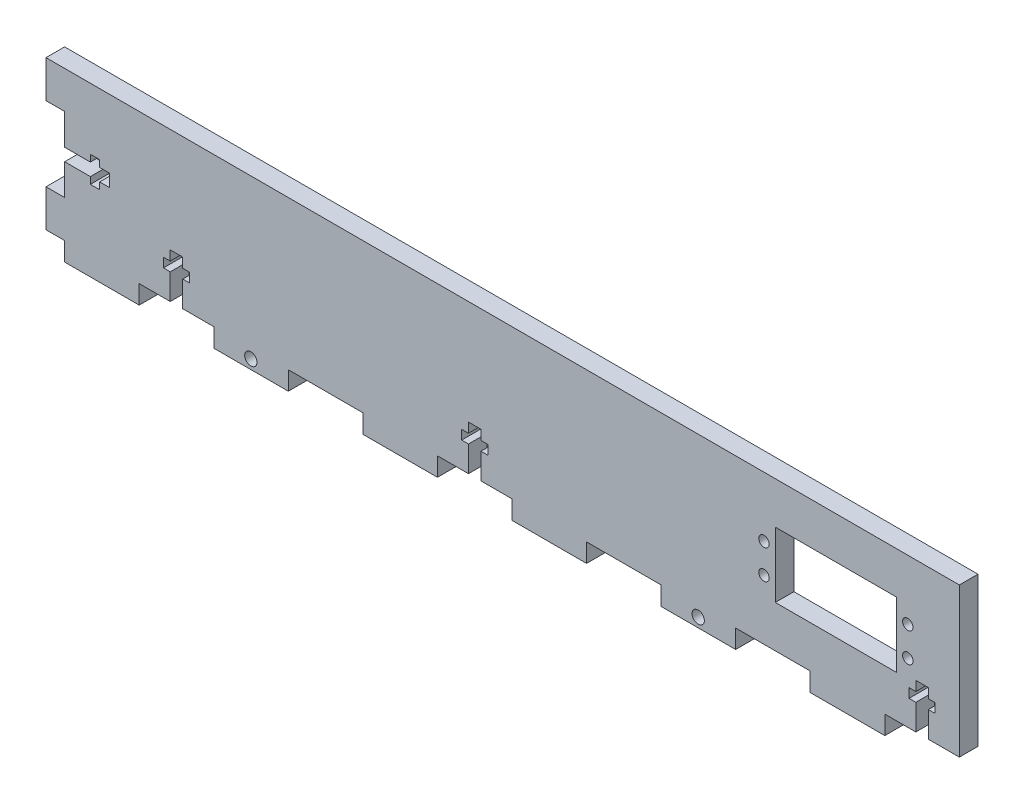
SolidWorks part; units mm, degrees
ref_plane "Front Plane" through (0, 0, 0) normal (0, 0, 1) x (1, 0, 0)
ref_plane "Top Plane" through (0, 0, 0) normal (0, 1, 0) x (1, 0, 0)
ref_plane "Right Plane" through (0, 0, 0) normal (1, 0, 0) x (0, 0, -1)
sketch "Sketch1" plane through (0, 0, 0) normal (0, 0, 1) x (1, 0, 0)
  line L0 (-262.733, -49.2353) -> (-262.733, 69.85) construction
  line L1 (42.067, 25.4) -> (-262.733, 25.4)
  line L2 (42.067, 25.4) -> (42.067, -25.4)
  line L3 (42.067, -25.4) -> (-262.733, -25.4)
  line L4 (-262.733, 25.4) -> (-262.733, -25.4)
  line L5 (63.0291, 0) -> (-62.7737, 0) construction
  line L6 (-19.6295, 10.033) -> (19.6295, 10.033) construction
  line L7 (19.6295, -10.033) -> (-19.6295, -10.033) construction
  line L8 (27.25, 6.27) -> (27.25, 8.0899) construction
  dimension "D1" = 50.8
  dimension "D2" = 14.817
extrude "Boss-Extrude1" add sketch "Sketch1" along normal blind 6.35
sketch "Sketch2" plane through (0, 0, 6.35) normal (0, 0, 1) x (1, 0, 0)
  line L0 (-41.9443, 0) -> (30.2812, 0) construction
  line L1 (-20.6375, 11.1125) -> (20.6375, 11.1125)
  line L2 (-20.6375, 11.1125) -> (-20.6375, -11.1125)
  line L3 (-20.6375, -11.1125) -> (20.6375, -11.1125)
  line L4 (20.6375, 11.1125) -> (20.6375, -11.1125)
  line L5 (-19.6295, 10.033) -> (19.6295, 10.033) construction
  line L6 (19.6295, -10.033) -> (-19.6295, -10.033) construction
  line L7 (0, 34.6052) -> (0, -28.4279) construction
  line L8 (-20.1295, -9.533) -> (-20.1295, 9.533) construction
  line L9 (20.1295, 9.533) -> (20.1295, -9.533) construction
  dimension "D1" = 22.225
  dimension "D2" = 41.275
extrude "Cut-Extrude1" cut sketch "Sketch2" against normal through all
ref_plane "Plane1" through (42.067, -25.4, 6.35) normal (1, 0, 0) x (0, 0, -1)
sketch "Sketch5" plane through (0, -25.4, 0) normal (0, -1, 0) x (1, 0, 0)
  line L0 (-262.733, 6.35) -> (42.067, 6.35) construction
  line L1 (16.667, 6.35) -> (-8.733, 6.35)
  line L2 (16.667, 6.35) -> (16.667, 0)
  line L3 (16.667, 0) -> (-8.733, 0)
  line L4 (-8.733, 6.35) -> (-8.733, 0)
  line L5 (-262.733, 0) -> (42.067, 0) construction
  dimension "D1" = 25.4
  dimension "D2" = 25.4
extrude "Boss-Extrude2" add sketch "Sketch5" along normal blind 6.35
pattern_linear "LPattern1" count 6 spacing 50.8 along (-1, 0, 0) of "Boss-Extrude2"
sketch "Sketch6" plane through (-262.733, 0, 0) normal (-1, 0, 0) x (0, 0, 1)
  line L0 (0, 25.4) -> (6.35, 25.4)
  line L1 (6.35, 25.4) -> (6.35, 12.7)
  line L2 (6.35, 25.4) -> (6.35, -31.75) construction
  line L3 (6.35, 12.7) -> (0, 12.7)
  line L4 (0, 25.4) -> (0, -31.75) construction
  line L5 (0, 12.7) -> (0, 25.4)
  dimension "D1" = 12.7
extrude "Boss-Extrude3" add sketch "Sketch6" along normal blind 6.35
pattern_linear "LPattern2" count 2 spacing 38.1 along (0, -1, 0) of "Boss-Extrude3"
sketch "Sketch7" plane through (0, 0, 6.35) normal (0, 0, 1) x (1, 0, 0)
  line L0 (-257.1687, 0) -> (-223.3079, 0) construction
  line L1 (-269.083, 12.7) -> (-262.733, 12.7) construction
  line L2 (-269.083, -12.7) -> (-262.733, -12.7) construction
  line L3 (-262.733, 12.7) -> (-262.733, -12.7) construction
  line B0 (-262.733, 2.1336) -> (-262.733, -2.1336)
  line B1 (-250.795, -2.1336) -> (-250.795, -4.445)
  line B2 (-250.795, -4.445) -> (-253.97, -4.445)
  line B3 (-253.97, -4.445) -> (-253.97, -2.1336)
  line B4 (-253.97, -2.1336) -> (-262.733, -2.1336)
  line B5 (-250.795, -2.1336) -> (-247.493, -2.1336)
  line B6 (-247.493, -2.1336) -> (-247.493, 2.1336)
  line B7 (-250.795, 2.1336) -> (-247.493, 2.1336)
  line B8 (-253.97, 2.1336) -> (-262.733, 2.1336)
  line B9 (-253.97, 4.445) -> (-253.97, 2.1336)
  line B10 (-250.795, 4.445) -> (-253.97, 4.445)
  line B11 (-250.795, 2.1336) -> (-250.795, 4.445)
sketch_block_instance "TSlot-1"
sketch_block "TSlot" parameters "D1"=3.302, "D2"=3.175
extrude "Cut-Extrude2" cut sketch "Sketch7" against normal through all
sketch "Sketch8" plane through (0, 0, 6.35) normal (0, 0, 1) x (1, 0, 0)
  line L0 (29.367, -1.7985) -> (29.367, -25.4) construction
  line L1 (16.667, -25.4) -> (42.067, -25.4) construction
  line L2 (42.067, -25.4) -> (42.067, 25.4) construction
  line L3 (16.667, -31.75) -> (16.667, -25.4) construction
  line L4 (-224.633, 2.3642) -> (-224.633, -25.4) construction
  line L5 (-237.333, -25.4) -> (-211.933, -25.4) construction
  line L6 (-237.333, -31.75) -> (-237.333, -25.4) construction
  line L7 (-211.933, -31.75) -> (-211.933, -25.4) construction
  line L8 (-123.033, 2.3642) -> (-123.033, -25.4) construction
  line L9 (-135.733, -25.4) -> (-110.333, -25.4) construction
  line L10 (-135.733, -31.75) -> (-135.733, -25.4) construction
  line L11 (-110.333, -31.75) -> (-110.333, -25.4) construction
  line B0 (-226.7666, -25.4) -> (-222.4994, -25.4)
  line B1 (-222.4994, -13.462) -> (-220.188, -13.462)
  line B2 (-220.188, -13.462) -> (-220.188, -16.637)
  line B3 (-220.188, -16.637) -> (-222.4994, -16.637)
  line B4 (-222.4994, -16.637) -> (-222.4994, -25.4)
  line B5 (-222.4994, -13.462) -> (-222.4994, -10.16)
  line B6 (-222.4994, -10.16) -> (-226.7666, -10.16)
  line B7 (-226.7666, -13.462) -> (-226.7666, -10.16)
  line B8 (-226.7666, -16.637) -> (-226.7666, -25.4)
  line B9 (-229.078, -16.637) -> (-226.7666, -16.637)
  line B10 (-229.078, -13.462) -> (-229.078, -16.637)
  line B11 (-226.7666, -13.462) -> (-229.078, -13.462)
  line B12 (-125.1666, -25.4) -> (-120.8994, -25.4)
  line B13 (-120.8994, -13.462) -> (-118.588, -13.462)
  line B14 (-118.588, -13.462) -> (-118.588, -16.637)
  line B15 (-118.588, -16.637) -> (-120.8994, -16.637)
  line B16 (-120.8994, -16.637) -> (-120.8994, -25.4)
  line B17 (-120.8994, -13.462) -> (-120.8994, -10.16)
  line B18 (-120.8994, -10.16) -> (-125.1666, -10.16)
  line B19 (-125.1666, -13.462) -> (-125.1666, -10.16)
  line B20 (-125.1666, -16.637) -> (-125.1666, -25.4)
  line B21 (-127.478, -16.637) -> (-125.1666, -16.637)
  line B22 (-127.478, -13.462) -> (-127.478, -16.637)
  line B23 (-125.1666, -13.462) -> (-127.478, -13.462)
  line B24 (27.2334, -25.4) -> (31.5006, -25.4)
  line B25 (31.5006, -13.462) -> (33.812, -13.462)
  line B26 (33.812, -13.462) -> (33.812, -16.637)
  line B27 (33.812, -16.637) -> (31.5006, -16.637)
  line B28 (31.5006, -16.637) -> (31.5006, -25.4)
  line B29 (31.5006, -13.462) -> (31.5006, -10.16)
  line B30 (31.5006, -10.16) -> (27.2334, -10.16)
  line B31 (27.2334, -13.462) -> (27.2334, -10.16)
  line B32 (27.2334, -16.637) -> (27.2334, -25.4)
  line B33 (24.922, -16.637) -> (27.2334, -16.637)
  line B34 (24.922, -13.462) -> (24.922, -16.637)
  line B35 (27.2334, -13.462) -> (24.922, -13.462)
sketch_block_instance "TSlot-2"
sketch_block_instance "TSlot-4"
sketch_block_instance "TSlot-5"
extrude "Cut-Extrude3" cut sketch "Sketch8" against normal through all
sketch "Sketch9" plane through (0, 0, 0) normal (0, 0, -1) x (-1, 0, 0)
  line L0 (44.7707, -31.75) -> (49.0379, -25.4) construction
  line L1 (59.533, -31.75) -> (34.133, -31.75) construction
  line L2 (44.7707, -31.75) -> (44.7707, -25.4) construction
  line L3 (49.0379, -31.75) -> (44.7707, -25.4) construction
  line L4 (49.0379, -25.4) -> (49.0379, -31.75) construction
  line L5 (197.1707, -31.75) -> (201.4379, -25.4) construction
  line L6 (197.1707, -31.75) -> (197.1707, -25.4) construction
  line L7 (211.933, -31.75) -> (186.533, -31.75) construction
  line L8 (201.4379, -31.75) -> (197.1707, -25.4) construction
  line L9 (201.4379, -25.4) -> (201.4379, -31.75) construction
  circle A0 centre (46.9043, -28.575) radius 2.0955
  circle A1 centre (199.3043, -28.575) radius 2.0955
  dimension "D1" = 4.191
extrude "Cut-Extrude4" cut sketch "Sketch9" against normal through all
sketch "Sketch10" plane through (0, 0, 0) normal (0, 0, -1) x (-1, 0, 0)
  circle A0 centre (24.5, -5) radius 1.778
  circle A1 centre (24.5, 5) radius 1.778
  circle A2 centre (-24.5, -5) radius 1.778
  circle A3 centre (-24.5, 5) radius 1.778
extrude "Cut-Extrude5" cut sketch "Sketch10" against normal through all
